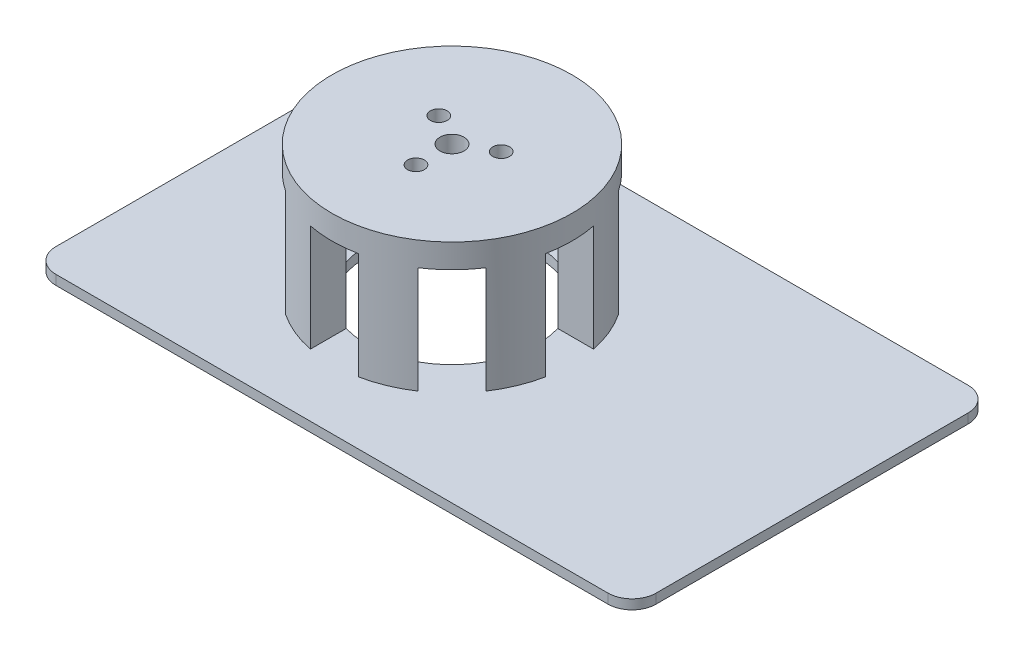
SolidWorks part; units mm, degrees
ref_plane "Front" through (0, 0, 0) normal (0, 0, 1) x (1, 0, 0)
ref_plane "Top" through (0, 0, 0) normal (0, 1, 0) x (1, 0, 0)
ref_plane "Right" through (0, 0, 0) normal (1, 0, 0) x (0, 0, -1)
sketch "Sketch1" plane through (0, 0, 0) normal (0, 1, 0) x (1, 0, 0)
  circle A0 centre (0, 0) radius 50
  dimension "D1" = 100
extrude "Boss-Extrude1" add sketch "Sketch1" along normal blind 58.5
sketch "Sketch2" plane through (0, 0, 0) normal (0, 1, 0) x (1, 0, 0)
  line L1 (-90, 75) -> (140, 75)
  line L2 (-100, 65) -> (-100, -65)
  line L3 (-90, -75) -> (140, -75)
  line L4 (150, 65) -> (150, -65)
  arc A1 (-100, -65) -> (-90, -75) centre (-90, -65) ccw
  arc A2 (140, -75) -> (150, -65) centre (140, -65) ccw
  arc A3 (140, 75) -> (150, 65) centre (140, 65) cw
  arc A4 (-90, 75) -> (-100, 65) centre (-90, 65) ccw
  point P7 (-100, 0)
  dimension "D1" = 150
  dimension "D4" = 10
  dimension "D2" = 150
  dimension "D3" = 100
extrude "Boss-Extrude2" add sketch "Sketch2" along normal blind 4 contours L2 A1 L3 A2 L4 A3 L1 A4
sketch "Sketch3" plane through (0, 58.5, 0) normal (0, 1, 0) x (1, 0, 0)
  circle A0 centre (0, 0) radius 5
  dimension "D1" = 10
extrude "Cut-Extrude1" cut sketch "Sketch3" against normal blind 20
sketch "Sketch4" plane through (0, 4, 0) normal (0, 1, 0) x (1, 0, 0)
  line L1 (99, 21) -> (141, 21)
  line L2 (99, 21) -> (99, -21)
  line L3 (99, -21) -> (141, -21)
  line L4 (141, 21) -> (141, -21)
  line L5 (99, 21) -> (141, -21) construction
  line L6 (99, -21) -> (141, 21) construction
  point P0 (120, 0)
  dimension "D1" = 42
  dimension "D2" = 120
sketch "Sketch5" plane through (0, 58.5, 0) normal (0, 1, 0) x (1, 0, 0)
  circle A0 centre (0, 0) radius 35.5
  dimension "D1" = 71
sketch "Sketch6" plane through (0, 0, 0) normal (0, -1, 0) x (1, 0, 0)
  circle A3 centre (0, 0) radius 35.5
  circle A4 centre (0, 0) radius 35.5
  dimension "D1" = 0
extrude "Cut-Extrude2" cut sketch "Sketch6" against normal offset from surface (48.5 mm away) 10 up to face at (0, 58.5, 5)
sketch "Sketch7" plane through (0, 0, 0) normal (0, 0, 1) x (1, 0, 0)
  line L0 (-90, 4) -> (140, 4) construction
  line L1 (-10, 4) -> (10, 4)
  line L2 (-10, 4) -> (-10, 48.5)
  line L3 (-10, 48.5) -> (10, 48.5)
  line L4 (10, 4) -> (10, 48.5)
  line L6 (35.5, 58.5) -> (-35.5, 58.5) construction
  point P8 (0, 48.5)
  dimension "D1" = 20
  dimension "D2" = 10
extrude "Cut-Extrude3" cut sketch "Sketch7" against normal through all both and the other way through all
pattern_circular "CirPattern1" count 8 over 360 about axis through (0, 58.5, 0) along (0, -1, 0) of "Cut-Extrude3"
sketch "Sketch8" plane through (0, 48.5, 0) normal (0, -1, 0) x (1, 0, 0)
  circle A0 centre (0, 15) radius 1.5
  circle A1 centre (12.9904, -7.5) radius 1.5
  circle A2 centre (-12.9904, -7.5) radius 1.5
  point P9 (0, 0)
  dimension "D1" = 3
  dimension "D2" = 15
  dimension "D3" = 3
extrude "Extrude-Thin1" add sketch "Sketch8" along normal blind 14.5 thin thin type one direction wall 2
extrude "Cut-Extrude4" cut sketch "Sketch8<2>" against normal through all
sketch "Sketch8<2>" plane through (0, 48.5, 0) normal (0, -1, 0) x (1, 0, 0) same geometry as "Sketch8"
sketch "Sketch9" plane through (0, 58.5, 0) normal (0, 1, 0) x (1, 0, 0)
  circle A0 centre (0, -15) radius 3.5
  circle A1 centre (-12.9904, 7.5) radius 1.5
  circle A2 centre (-12.9904, 7.5) radius 1.5
  circle A3 centre (12.9904, 7.5) radius 1.5
  circle A4 centre (12.9904, 7.5) radius 1.5
  circle A5 centre (0, -15) radius 1.5
  circle A6 centre (0, -15) radius 1.5
  circle A7 centre (-12.9904, 7.5) radius 3.5
  circle A8 centre (12.9904, 7.5) radius 3.5
  dimension "D1" = 0
  dimension "D2" = 0
  dimension "D3" = 0
  dimension "D4" = 2
extrude "Cut-Extrude5" cut sketch "Sketch9" against normal blind 5
fillet "Fillet1" radius 2 3 edges at (12.9904, 48.5, -4) (-12.9904, 48.5, -4) (0, 48.5, 18.5)
